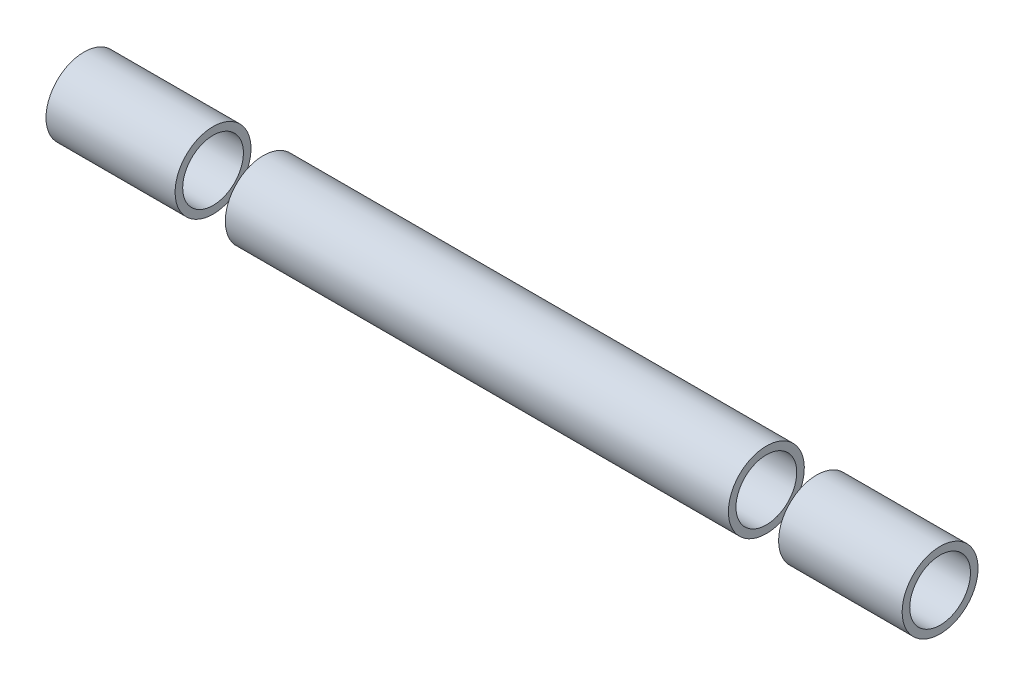
SolidWorks part; units mm, degrees
material "PC High Viscosity"
ref_plane "Front Plane" through (0, 0, 0) normal (0, 0, 1) x (1, 0, 0)
ref_plane "Top Plane" through (0, 0, 0) normal (0, 1, 0) x (1, 0, 0)
ref_plane "Right Plane" through (0, 0, 0) normal (1, 0, 0) x (0, 0, -1)
sketch "Sketch1" plane through (0, 0, 0) normal (1, 0, 0) x (0, 0, -1)
  circle A0 centre (0, 0) radius 15.875
  dimension "D1" = 31.75
extrude "Extrude-Thin1" add sketch "Sketch1" along normal mid plane 360.299 thin thin type one direction reverse wall 3.175
sketch "Sketch2" plane through (0, 0, 0) normal (0, 0, 1) x (1, 0, 0)
  line L0 (-180.1495, -15.875) -> (180.1495, -15.875) construction
  line L1 (105.1745, -15.875) -> (126.1745, -15.875)
  line L2 (105.1745, -15.875) -> (105.1745, 15.875)
  line L3 (105.1745, 15.875) -> (126.1745, 15.875)
  line L4 (126.1745, -15.875) -> (126.1745, 15.875)
  line L5 (180.1495, 15.875) -> (-180.1495, 15.875) construction
  line L6 (180.1495, -15.875) -> (180.1495, 15.875) construction
  line L7 (0, 0) -> (0, 11.1276) construction
  line L8 (-126.1745, -15.875) -> (-126.1745, 15.875)
  line L9 (-105.1745, 15.875) -> (-126.1745, 15.875)
  line L10 (-105.1745, -15.875) -> (-105.1745, 15.875)
  line L11 (-105.1745, -15.875) -> (-126.1745, -15.875)
  line L13 (180.1495, -15.875) -> (177.8254, -15.875)
  line L14 (180.1495, -15.875) -> (180.1495, 15.875)
  line L15 (180.1495, 15.875) -> (177.8254, 15.875)
  line L16 (177.8254, -15.875) -> (177.8254, 15.875)
  dimension "D1" = 53.975
  dimension "D2" = 21
  dimension "D3" = 2.3241
extrude "Cut-Extrude1" cut sketch "Sketch2" against normal through all both and the other way through all
equation "\"D2@Sketch2\"=21mm"
